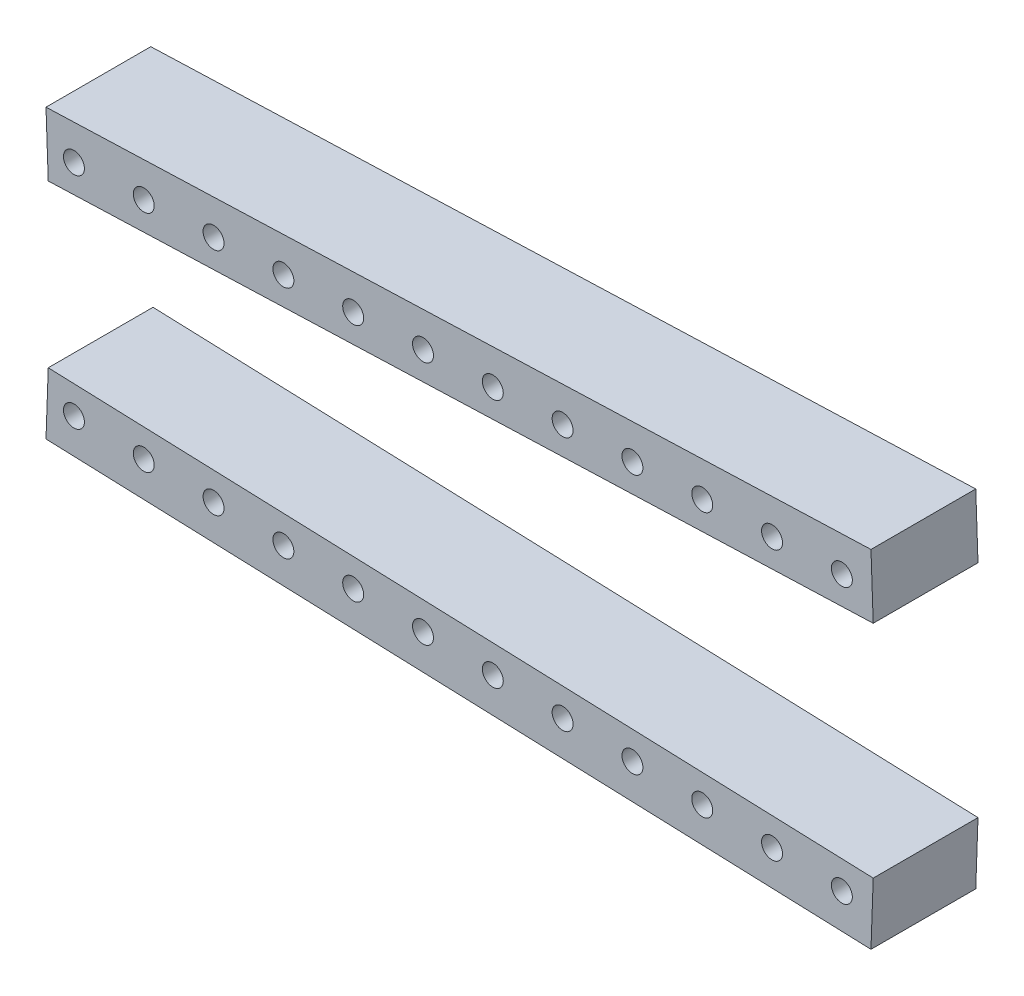
SolidWorks part; units mm, degrees
ref_plane "前视基准面" through (0, 0, 0) normal (0, 0, 1) x (1, 0, 0)
ref_plane "上视基准面" through (0, 0, 0) normal (0, 1, 0) x (1, 0, 0)
ref_plane "右视基准面" through (0, 0, 0) normal (1, 0, 0) x (0, 0, -1)
other "Configuration Table"
sketch "草图1" plane through (0, 0, 0) normal (0, 0, 1) x (1, 0, 0)
  line L0 (0, 0) -> (140, 0)
  line L1 (0, 35) -> (140, 25)
  line L2 (0, -35) -> (140, -25)
  circle A0 centre (0, 0) radius 35
  circle A1 centre (140, 0) radius 25
  dimension "D1" = 70
  dimension "D3" = 50
  dimension "D2" = 140
extrude "凸台-拉伸3" add sketch "草图1" along normal blind 5 contours A0 L1 L2 | A1 L0 A0 L2 | A1 L1 A0 L0 | A1 region at (72.7482, 16.0498, 0) region at (-0.0004, 0, 0) region at (72.7482, -16.0498, 0) region at (122.8223, 17.1777, 0)
sketch "草图4" plane through (0, 0, 5) normal (0, 0, 1) x (1, 0, 0)
  line L1 (-5, -5) -> (5, -5)
  line L2 (-5, -5) -> (-5, 5)
  line L3 (-5, 5) -> (5, 5)
  line L4 (5, -5) -> (5, 5)
  line L5 (-5, -5) -> (5, 5) construction
  line L6 (-5, 5) -> (5, -5) construction
  line L7 (135, -5) -> (145, -5)
  line L8 (135, -5) -> (135, 5)
  line L9 (135, 5) -> (145, 5)
  line L10 (145, -5) -> (145, 5)
  line L11 (135, -5) -> (145, 5) construction
  line L12 (135, 5) -> (145, -5) construction
  circle A0 centre (0, 0) radius 4
  circle A1 centre (-5, 5) radius 1.5
  circle A2 centre (5, 5) radius 1.5
  circle A3 centre (5, -5) radius 1.5
  circle A4 centre (-5, -5) radius 1.5
  circle A5 centre (140, 0) radius 4
  circle A6 centre (135, 5) radius 1.5
  circle A7 centre (145, 5) radius 1.5
  circle A8 centre (145, -5) radius 1.5
  circle A9 centre (135, -5) radius 1.5
  dimension "D1" = 8
  dimension "D4" = 3
  dimension "D6" = 8
  dimension "D9" = 3
  dimension "D2" = 10
  dimension "D3" = 10
  dimension "D7" = 10
  dimension "D8" = 10
  dimension "D5" = 4
  dimension "D10" = 4
extrude "切除-拉伸3" cut sketch "草图4" against normal blind 5 contours A5 | A0 | L2 A4 L1 | L1 A4 L2 | A6 | A9 | A8 | A7 | A1 | A2 | A3 region at (-4.3634, -4.3634, 5) region at (-5.2122, -5.2122, 5) region at (0, 0, 5) region at (140, 0, 5)
sketch "草图5" plane through (0, 0, 5) normal (0, 0, 1) x (1, 0, 0)
  circle A0 centre (0, 0) radius 11
  circle A1 centre (140, 0) radius 11
  dimension "D1" = 22
  dimension "D2" = 22
extrude "切除-拉伸4" cut sketch "草图5" against normal blind 2
sketch "草图6" plane through (0, 0, 5) normal (0, 0, 1) x (1, 0, 0)
  circle A0 centre (0, 0) radius 30
  circle A1 centre (0, 30) radius 1.5
  circle A2 centre (15, 25.9808) radius 1.5
  circle A3 centre (25.9808, 15) radius 1.5
  circle A4 centre (30, 0) radius 1.5
  circle A5 centre (25.9808, -15) radius 1.5
  circle A6 centre (15, -25.9808) radius 1.5
  circle A7 centre (0, -30) radius 1.5
  circle A8 centre (-15, -25.9808) radius 1.5
  circle A9 centre (-25.9808, -15) radius 1.5
  circle A10 centre (-30, 0) radius 1.5
  circle A11 centre (-25.9808, 15) radius 1.5
  circle A12 centre (-15, 25.9808) radius 1.5
  circle A13 centre (140, 0) radius 20
  circle A14 centre (140, 20) radius 1.5
  circle A15 centre (150, 17.3205) radius 1.5
  circle A16 centre (157.3205, 10) radius 1.5
  circle A17 centre (160, 0) radius 1.5
  circle A18 centre (157.3205, -10) radius 1.5
  circle A19 centre (150, -17.3205) radius 1.5
  circle A20 centre (140, -20) radius 1.5
  circle A21 centre (130, -17.3205) radius 1.5
  circle A22 centre (122.6795, -10) radius 1.5
  circle A23 centre (120, 0) radius 1.5
  circle A24 centre (122.6795, 10) radius 1.5
  circle A25 centre (130, 17.3205) radius 1.5
  point P29 (0, 0)
  dimension "D1" = 60
  dimension "D2" = 3
  dimension "D4" = 40
  dimension "D5" = 3
  dimension "D3" = 12
  dimension "D6" = 12
extrude "切除-拉伸6" cut sketch "草图6" against normal through all contours A0 A12 | A11 | A12 | A1 | A2 | A3 | A4 | A5 | A6 | A7 | A8 | A9 | A10 | A25 | A14 | A15 | A16 | A17 | A18 | A19 | A20 | A21 | A22 | A23 | A24 region at (-14.6783, 25.4236, 5)
sketch "草图7" plane through (0, 0, 5) normal (0, 0, 1) x (1, 0, 0)
  line L0 (140, 25) -> (0, 20)
  line L1 (140, -25) -> (0, -20)
  circle A0 centre (0, 0) radius 20
  circle A1 centre (140, 0) radius 25
  circle M1 centre (15, -25.9808) radius 1.5
  circle M2 centre (0, -30) radius 1.5
  circle M3 centre (-15, -25.9808) radius 1.5
  circle M4 centre (-25.9808, -15) radius 1.5
  circle M5 centre (-30, 0) radius 1.5
  circle M20 centre (15, 25.9808) radius 1.5
  circle M21 centre (-15, 25.9808) radius 1.5
  circle M22 centre (-25.9808, 15) radius 1.5
  circle M23 centre (0, 30) radius 1.5
  line M27 (0, -35) -> (140, -25)
  line M29 (140, 25) -> (0, 35)
  arc M30 (0, 35) -> (0, -35) centre (0, 0) ccw
  dimension "D1" = 40
extrude "切除-拉伸7" cut sketch "草图7" against normal blind 10 contours A1 L1 A0 L0 M29 M30 M27 M1 M3 M5 M21 M23 M22 M20 M4 M2 region at (69.041, 24.3518, 5)
sketch "草图8" plane through (0, 0, 5) normal (0, 0, 1) x (1, 0, 0)
  circle A1 centre (0, 0) radius 11
extrude "切除-拉伸8" cut sketch "草图8" against normal blind 10
sketch "草图9" plane through (0, 0, 5) normal (0, 0, 1) x (1, 0, 0)
  circle A0 centre (0, 0) radius 15
  circle A1 centre (0, 15) radius 1.5
  circle A2 centre (10.6066, 10.6066) radius 1.5
  circle A3 centre (15, 0) radius 1.5
  circle A4 centre (10.6066, -10.6066) radius 1.5
  circle A5 centre (0, -15) radius 1.5
  circle A6 centre (-10.6066, -10.6066) radius 1.5
  circle A7 centre (-15, 0) radius 1.5
  circle A8 centre (-10.6066, 10.6066) radius 1.5
  dimension "D1" = 30
  dimension "D2" = 3
  dimension "D3" = 8
extrude "切除-拉伸9" cut sketch "草图9" against normal blind 10 contours A0 A4 | A2 | A3 | A4 | A5 | A6 | A7 | A8 | A1 region at (11.0471, -11.0471, 5)
sketch "草图10" plane through (0, 0, 3) normal (0, 0, 1) x (1, 0, 0)
  circle A0 centre (140, 0) radius 5
  dimension "D1" = 10
extrude "切除-拉伸10" cut sketch "草图10" against normal blind 10
sketch "草图11" plane through (0, 0, 5) normal (0, 0, 1) x (1, 0, 0)
  line L0 (140, 0) -> (110, 0)
  line L1 (140, 0) -> (130, 0)
  line L2 (110, 0) -> (105.5, 0)
  line L3 (150, -10) -> (110, -10)
  line L4 (150, -10) -> (150, 10)
  line L5 (150, 10) -> (110, 10)
  line L6 (110, -10) -> (110, 10)
  line L7 (150, -10) -> (110, 10) construction
  line L8 (150, 10) -> (110, -10) construction
  line L9 (105.5, 0) -> (105.5, 5)
  line L10 (130, -1000) -> (130, 49000) construction
  circle A0 centre (105.5, 5) radius 2
  circle A1 centre (105.5, -5) radius 2
  circle A2 centre (154.5, -5) radius 2
  circle A3 centre (154.5, 5) radius 2
  circle M14 centre (140, 0) radius 11
  circle M16 centre (122.6795, 10) radius 1.5
  circle M20 centre (120, 0) radius 1.5
  circle M21 centre (122.6795, -10) radius 1.5
  dimension "D6" = 4
  dimension "D1" = 30
  dimension "D2" = 10
  dimension "D3" = 20
  dimension "D4" = 4.5
  dimension "D5" = 5
extrude "切除-拉伸11" cut sketch "草图11" against normal blind 10 contours A0 | A1 | A3 | A2 | L6 L3 L0 M21 M14 M20 | L5 L3 L4 | L6 L0 L5 M20 M14 M16 | L4 L5 M14 | L3 L4 M14 region at (120.4472, -5.2396, 5) region at (120.4472, 5.2396, 5) region at (130.9864, 5.7844, 5) region at (104.1258, 6.3742, 5) region at (148.4191, 8.4191, 5) region at (148.4191, -8.4191, 5) region at (105.5, -5, 5) region at (154.5, -5, 5) region at (154.5, 5, 5)
sketch "草图12" plane through (0, 0, 5) normal (0, 0, 1) x (1, 0, 0)
  line L0 (110, 10) -> (44831.3595, -22350.6798) construction
  line L1 (150, 10) -> (-44571.3595, -22350.6798) construction
  line L3 (109.5, -11) -> (150.5, -11)
  line L4 (109.5, -11) -> (109.5, 11)
  line L5 (109.5, 11) -> (150.5, 11)
  line L6 (150.5, -11) -> (150.5, 11)
  line L7 (109.5, -11) -> (150.5, 11) construction
  line L8 (109.5, 11) -> (150.5, -11) construction
  point P8 (130, 0)
  dimension "D1" = 41
  dimension "D2" = 22
extrude "切除-拉伸12" cut sketch "草图12" against normal blind 10
sketch "草图13" plane through (0, 0, 5) normal (0, 0, 1) x (1, 0, 0)
  line L0 (0.1785, -15.0032) -> (138.395, -19.9395)
  line L1 (0, -20) -> (138.2166, -24.9363)
  circle A0 centre (0, -15) radius 1.5
  circle A1 centre (9.9936, -15.3569) radius 1.5
  circle A2 centre (19.9873, -15.7138) radius 1.5
  circle A3 centre (29.9809, -16.0707) radius 1.5
  circle A4 centre (39.9745, -16.4277) radius 1.5
  circle A5 centre (49.9681, -16.7846) radius 1.5
  circle A6 centre (59.9618, -17.1415) radius 1.5
  circle A7 centre (69.9554, -17.4984) radius 1.5
  circle A8 centre (79.949, -17.8553) radius 1.5
  circle A9 centre (89.9427, -18.2122) radius 1.5
  circle A10 centre (99.9363, -18.5692) radius 1.5
  circle A11 centre (109.9299, -18.9261) radius 1.5
  circle A12 centre (119.9235, -19.283) radius 1.5
  circle A13 centre (129.9172, -19.6399) radius 1.5
  circle A14 centre (139.9108, -19.9968) radius 1.5
  circle M27 centre (130, -17.3205) radius 1.5
  dimension "D1" = 5
  dimension "D2" = 15
extrude "切除-拉伸13" cut sketch "草图13" against normal blind 10 contours L0 A1 | L0 A1 | L0 A13 | A13 L0 M27 | A2 | A3 | A4 | A5 | A6 | A7 | A9 | A8 | A10 | A11 | A12 region at (129.9337, -19.1762, 5) region at (129.8945, -20.2744, 5) region at (10.0164, -14.719, 5) region at (9.971, -15.9914, 5)
sketch "草图14" plane through (0, 0, 5) normal (0, 0, 1) x (1, 0, 0)
  circle A0 centre (130, -17.3205) radius 1.5
  circle A1 centre (129.9172, -19.6399) radius 1.5
extrude "凸台-拉伸4" add sketch "草图14" against normal blind 5 contours A1 A0 region at (130.0059, -17.1551, 5)
sketch "草图15" plane through (0, 0, 5) normal (0, 0, 1) x (1, 0, 0)
  circle A0 centre (25.9808, 15) radius 1.5
  circle A1 centre (30, 0) radius 1.5
  circle A2 centre (25.9808, -15) radius 1.5
extrude "凸台-拉伸6" add sketch "草图15" against normal blind 5
sketch "草图16" plane through (0, 0, 5) normal (0, 0, 1) x (1, 0, 0)
  line L0 (0, 20) -> (140, 25)
  line L1 (0.1785, 15.0032) -> (140.1785, 20.0032)
  arc A0 (138.2166, -24.9363) -> (138.2166, 24.9363) centre (140, 0) ccw construction
  circle A1 centre (0, 15) radius 1.5
  circle A2 centre (9.9936, 15.3569) radius 1.5
  circle A3 centre (19.9873, 15.7138) radius 1.5
  circle A4 centre (29.9809, 16.0707) radius 1.5
  circle A5 centre (39.9745, 16.4277) radius 1.5
  circle A6 centre (49.9681, 16.7846) radius 1.5
  circle A7 centre (59.9618, 17.1415) radius 1.5
  circle A8 centre (69.9554, 17.4984) radius 1.5
  circle A9 centre (79.949, 17.8553) radius 1.5
  circle A10 centre (89.9427, 18.2122) radius 1.5
  circle A11 centre (99.9363, 18.5692) radius 1.5
  circle A12 centre (109.9299, 18.9261) radius 1.5
  circle A13 centre (119.9235, 19.283) radius 1.5
  circle A14 centre (129.9172, 19.6399) radius 1.5
  circle A15 centre (139.9108, 19.9968) radius 1.5
  dimension "D1" = 5
  dimension "D2" = 15
extrude "切除-拉伸14" cut sketch "草图16" against normal blind 5 contours L1 A6 | L1 A6 | L1 A7 | L1 A7 | L1 A8 | L1 A8 | A2 | A3 | A4 | A5 | A9 | A10 | A11 | A12 | A13 | A14 region at (69.9327, 18.1329, 5) region at (69.9782, 16.8605, 5) region at (59.9391, 17.776, 5) region at (59.9846, 16.5036, 5) region at (49.9455, 17.4191, 5) region at (49.9909, 16.1466, 5)
sketch "草图17" plane through (0, 0, 5) normal (0, 0, 1) x (1, 0, 0)
  circle A0 centre (130, 17.3205) radius 1.5
  circle A1 centre (129.9172, 19.6399) radius 1.5
extrude "凸台-拉伸7" add sketch "草图17" against normal blind 5 contours A1 A0 region at (130.0059, 17.1551, 5)
sketch "草图18" plane through (0, 0, 5) normal (0, 0, 1) x (1, 0, 0)
  line L2 (138.5735, 14.9427) -> (0.3569, 10.0064)
  line L3 (138.5735, 14.9427) -> (0.3569, 10.0064)
  line L5 (138.5735, -14.9427) -> (0.3569, -10.0064)
  line L6 (138.5735, -14.9427) -> (0.3569, -10.0064)
  circle A0 centre (0, 0) radius 25
  circle A1 centre (0, 0) radius 100
  dimension "D1" = 50
  dimension "D2" = 200
  dimension "D3" = 10
  dimension "D4" = 10
extrude "切除-拉伸15" cut sketch "草图18" against normal blind 5 contours L6 A1 L3 A0 region at (63.3314, 0, 5)
sketch "草图19" plane through (0, 0, 5) normal (0, 0, 1) x (1, 0, 0)
  line L2 (99.0445, 14.5316) -> (22.5117, 11.7983)
  line L3 (134.9707, 15.8146) -> (6.5499, 11.2282)
  line L4 (16.3089, 11.5767) -> (15.9877, 20.571)
  line L5 (99.0445, -14.5316) -> (22.5117, -11.7983)
  line L6 (134.4063, -15.7945) -> (10.6063, -11.3731)
  line L7 (138.2166, 24.9363) -> (0, 20) construction
  line L8 (16.3089, -11.5767) -> (15.9877, -20.571)
  line L9 (138.2166, -24.9363) -> (0, -20) construction
  line L10 (15.9877, -20.571) -> (0, -20)
  line L11 (15.9877, 20.571) -> (0, 20)
  circle A1 centre (140, 0) radius 16.7558
  circle A2 centre (0, 0) radius 20
  dimension "D1" = 1
  dimension "D2" = 1
extrude "切除-拉伸19" cut sketch "草图19" against normal blind 5 contours A2 | A2 L4 L11 | A2 L10 L8 | A1 | A2 L6 A1 L3 region at (75.0685, 0, 5) region at (140, 0, 5) region at (12.134, 17.8788, 5) region at (0, 0, 5) region at (12.134, -17.8788, 5)
sketch "草图21" plane through (0, 0, 5) normal (0, 0, 1) x (1, 0, 0)
  line L0 (134.4063, 15.7945) -> (134.0851, 24.7888)
  line L1 (138.2166, 24.9363) -> (15.9877, 20.571) construction
  line L2 (134.4063, -15.7945) -> (134.0851, -24.7888)
  line L3 (138.2166, -24.9363) -> (15.9877, -20.571) construction
  circle A0 centre (140, 0) radius 25
  arc M1 (156.2593, 4.0487) -> (156.2593, -4.0487) centre (140, 0) cw
  arc M2 (156.2593, -4.0487) -> (155.299, -6.8335) centre (154.5, -5) cw
  arc M3 (155.299, -6.8335) -> (134.4063, -15.7945) centre (140, 0) cw
  line M6 (15.9877, -20.571) -> (138.2166, -24.9363)
  arc M7 (138.2166, -24.9363) -> (138.2166, 24.9363) centre (140, 0) ccw
  line M8 (138.2166, 24.9363) -> (15.9877, 20.571)
  arc M11 (134.4063, 15.7945) -> (155.299, 6.8335) centre (140, 0) cw
  arc M12 (155.299, 6.8335) -> (156.2593, 4.0487) centre (154.5, 5) cw
  circle M37 centre (140, 20) radius 1.5
  circle M38 centre (150, 17.3205) radius 1.5
  circle M39 centre (157.3205, 10) radius 1.5
  circle M40 centre (160, 0) radius 1.5
  circle M41 centre (157.3205, -10) radius 1.5
  circle M42 centre (150, -17.3205) radius 1.5
  circle M43 centre (140, -20) radius 1.5
extrude "切除-拉伸20" cut sketch "草图21" against normal blind 5 contours A0 L0 L2 M7 M11 M12 M1 M2 M3 M38 M40 M42 M43 M41 M39 M37 | A0 L0 M8 | A0 L2 M6 region at (134.8419, 20.0655, 5) region at (135.2564, 24.6804, 5) region at (135.2564, -24.6804, 5)
sketch "草图22" plane through (0, 0, 0) normal (0, 0, -1) x (-1, 0, 0)
  line L0 (-134.0851, 24.7888) -> (-134.4063, 15.7945)
  line L1 (-134.4063, 15.7945) -> (-16.3089, 11.5767)
  line L2 (-16.3089, 11.5767) -> (-15.9877, 20.571)
  line L3 (-15.9877, 20.571) -> (-134.0851, 24.7888)
  line L4 (-134.4063, -15.7945) -> (-134.0851, -24.7888)
  line L5 (-134.0851, -24.7888) -> (-15.9877, -20.571)
  line L6 (-15.9877, -20.571) -> (-16.3089, -11.5767)
  line L7 (-16.3089, -11.5767) -> (-134.4063, -15.7945)
extrude "凸台-拉伸8" add sketch "草图22" along normal blind 10
sketch "草图23" plane through (0, 0, 5) normal (0, 0, 1) x (1, 0, 0)
  circle A0 centre (19.9873, 15.7138) radius 1.5
  circle A1 centre (29.9809, 16.0707) radius 1.5
  circle A2 centre (39.9745, 16.4277) radius 1.5
  circle A3 centre (49.9681, 16.7846) radius 1.5
  circle A4 centre (59.9618, 17.1415) radius 1.5
  circle A5 centre (69.9554, 17.4984) radius 1.5
  circle A6 centre (79.949, 17.8553) radius 1.5
  circle A7 centre (89.9427, 18.2122) radius 1.5
  circle A8 centre (99.9363, 18.5692) radius 1.5
  circle A9 centre (109.9299, 18.9261) radius 1.5
  circle A10 centre (119.9235, 19.283) radius 1.5
  circle A11 centre (129.9172, 19.6399) radius 1.5
  circle A12 centre (129.9172, -19.6399) radius 1.5
  circle A13 centre (119.9235, -19.283) radius 1.5
  circle A14 centre (109.9299, -18.9261) radius 1.5
  circle A15 centre (99.9363, -18.5692) radius 1.5
  circle A16 centre (89.9427, -18.2122) radius 1.5
  circle A17 centre (79.949, -17.8553) radius 1.5
  circle A18 centre (69.9554, -17.4984) radius 1.5
  circle A19 centre (59.9618, -17.1415) radius 1.5
  circle A20 centre (49.9681, -16.7846) radius 1.5
  circle A21 centre (39.9745, -16.4277) radius 1.5
  circle A22 centre (29.9809, -16.0707) radius 1.5
  circle A23 centre (19.9873, -15.7138) radius 1.5
extrude "切除-拉伸21" cut sketch "草图23" against normal blind 15
